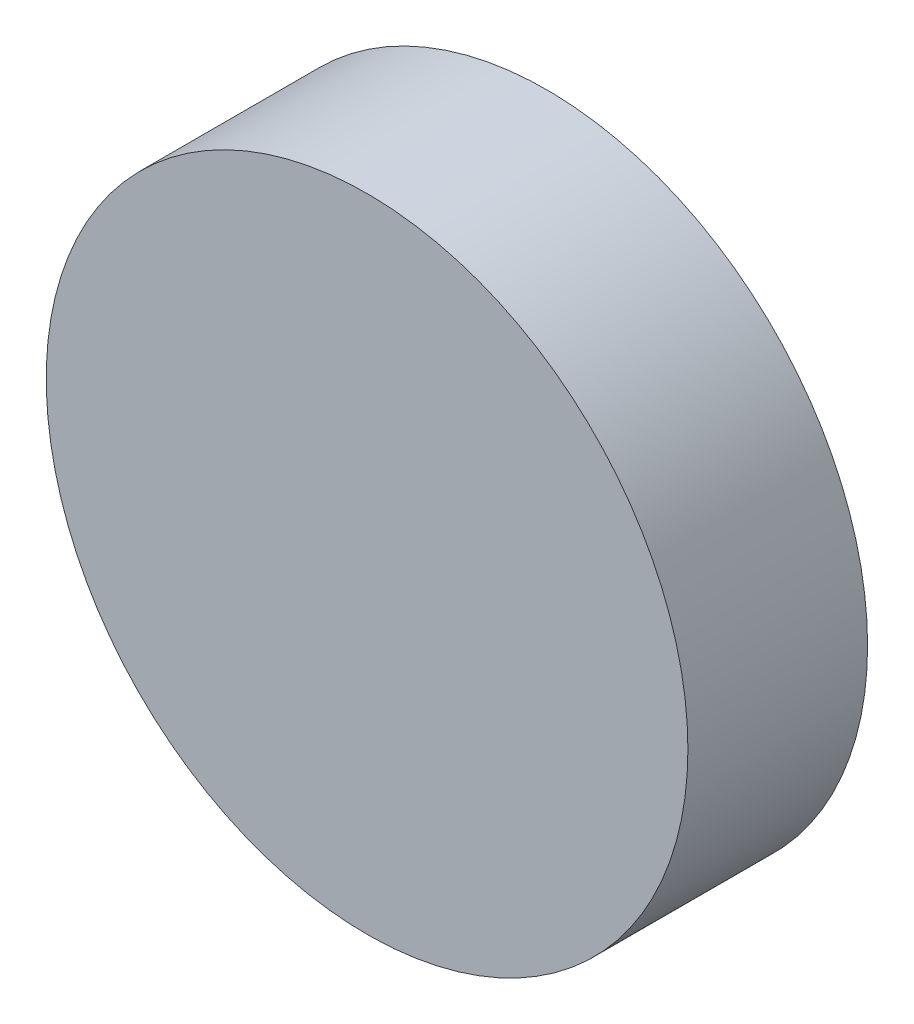
SolidWorks part; units mm, degrees
ref_plane "Спереди" through (0, 0, 0) normal (0, 0, 1) x (1, 0, 0)
ref_plane "Сверху" through (0, 0, 0) normal (0, 1, 0) x (1, 0, 0)
ref_plane "Справа" through (0, 0, 0) normal (1, 0, 0) x (0, 0, -1)
other "Configuration Table"
sketch "Эскиз1" plane through (0, 0, 0) normal (0, 0, 1) x (1, 0, 0)
  circle A0 centre (0, 0) radius 62.5
extrude "Колесо Ø125 × 35 (упрощено)" add sketch "Эскиз1" along normal blind 17.5 and the other way blind 17.5
